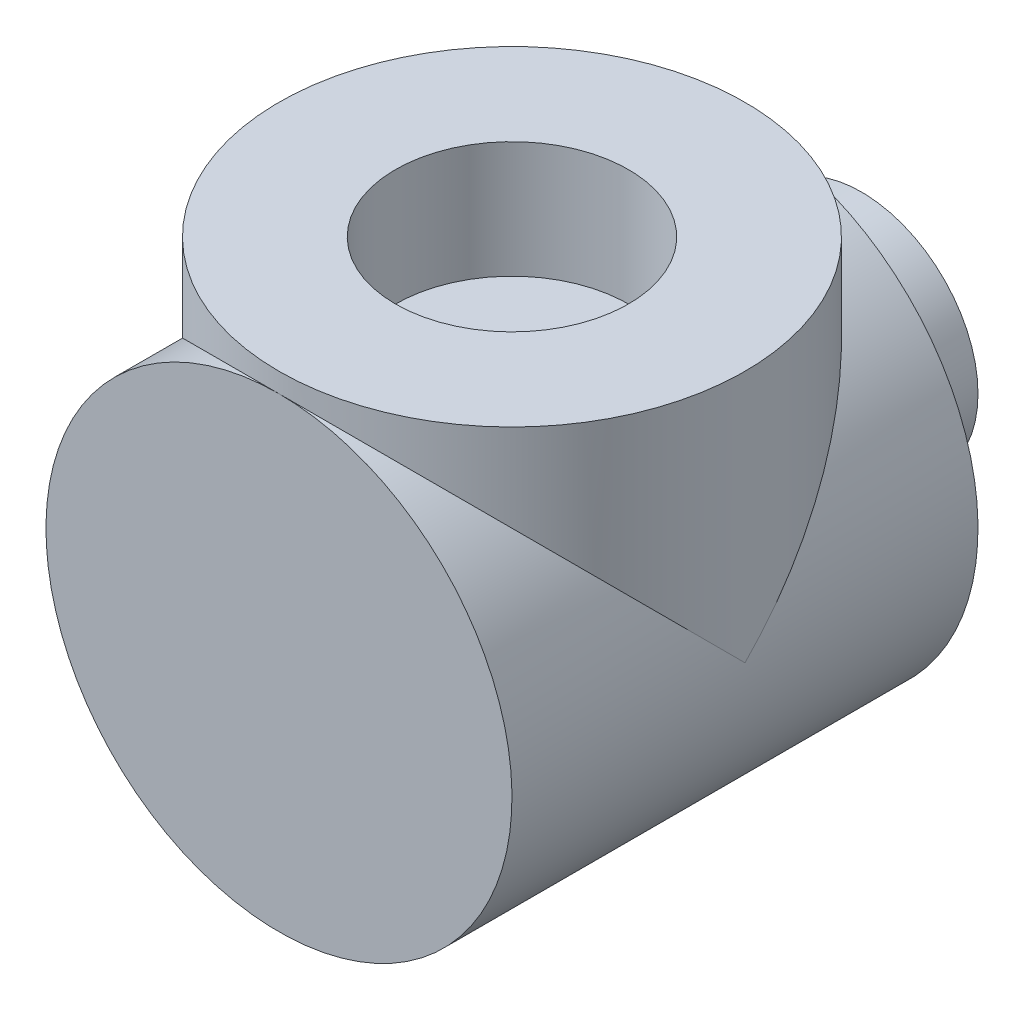
SolidWorks part; units mm, degrees
material "1060 Alloy"
ref_plane "Front Plane" through (0, 0, 0) normal (0, 0, 1) x (1, 0, 0)
ref_plane "Top Plane" through (0, 0, 0) normal (0, 1, 0) x (1, 0, 0)
ref_plane "Right Plane" through (0, 0, 0) normal (1, 0, 0) x (0, 0, -1)
sketch "Sketch1" plane through (0, 0, 0) normal (0, 0, 1) x (1, 0, 0)
  circle A0 centre (0, 0) radius 30
  circle A1 centre (0, 0) radius 15
  dimension "D1" = 60
  dimension "D2" = 30
extrude "Boss-Extrude1" add sketch "Sketch1" along normal mid plane 60 contours A1 | A0 A1 region at (-29.1515, 0, 0) region at (0, 0, 0)
sketch "Sketch2" plane through (0, 0, 0) normal (0, 1, 0) x (1, 0, 0)
  circle A0 centre (0, 0) radius 30
  circle A1 centre (0, 0) radius 15
  dimension "D1" = 60
  dimension "D2" = 30
extrude "Boss-Extrude2" add sketch "Sketch2" along normal blind 32.5 contours A1 | A0 A1 region at (-29.1515, 0, 0) region at (0, 0, 0)
extrude "Cut-Extrude2" cut sketch "Sketch2<3>" against normal blind 15 from surface contours A1 region at (0, 0, 0) starting at face at (0, 32.5, 30)
sketch "Sketch2<3>" plane through (0, 0, 0) normal (0, 1, 0) x (1, 0, 0) same geometry as "Sketch2"
extrude "Boss-Extrude3" add sketch "Sketch1<4>" against normal blind 15 from surface contours A1 region at (0, 0, 0) starting at face at (30, 0, -30)
sketch "Sketch1<4>" plane through (0, 0, 0) normal (0, 0, 1) x (1, 0, 0) same geometry as "Sketch1"
